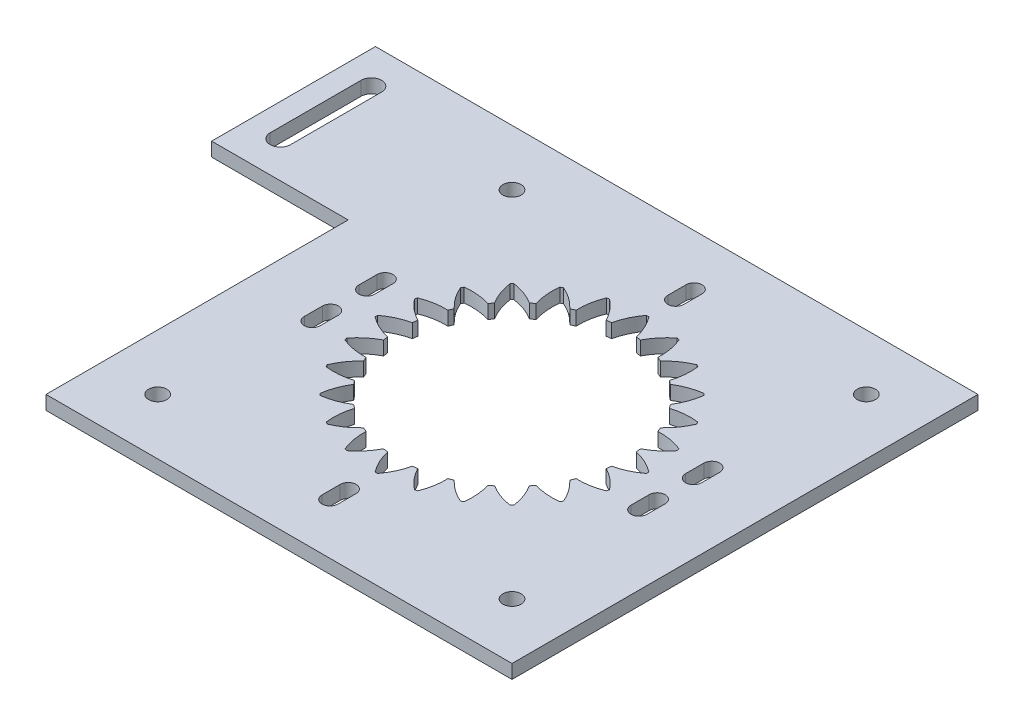
SolidWorks part; units mm, degrees
ref_plane "Front Plane" through (0, 0, 0) normal (0, 0, 1) x (1, 0, 0)
ref_plane "Top Plane" through (0, 0, 0) normal (0, 1, 0) x (1, 0, 0)
ref_plane "Right Plane" through (0, 0, 0) normal (1, 0, 0) x (0, 0, -1)
sketch "Sketch4" plane through (0, 0, 0) normal (0, 0, 1) x (1, 0, 0)
  line L0 (0, 0) -> (0, 40.0324) construction
sketch "Sketch1" plane through (0, 0, 0) normal (0, 1, 0) x (1, 0, 0)
  line L1 (-51.2, -51.2) -> (51.2, -51.2)
  line L2 (-51.2, -51.2) -> (-51.2, 15.2)
  line L3 (-51.2, 51.2) -> (51.2, 51.2)
  line L4 (51.2, -51.2) -> (51.2, 51.2)
  line L5 (-51.2, -51.2) -> (51.2, 51.2) construction
  line L6 (-51.2, 51.2) -> (51.2, -51.2) construction
  line L7 (-51.2, 51.2) -> (-81.2, 51.2)
  line L9 (-51.2, 15.2) -> (-81.2, 15.2)
  line L10 (-81.2, 51.2) -> (-81.2, 15.2)
  point P0 (0, 0)
  dimension "D1" = 102.4
  dimension "D2" = 102.4
  dimension "D3" = 30
  dimension "D4" = 36
extrude "Boss-Extrude1" add sketch "Sketch1" along normal blind 3.05
sketch "Sketch2" plane through (0, 3.05, 0) normal (0, 1, 0) x (1, 0, 0)
  arc B0 (7.4382, 28.8707) -> (3.7536, 24.4637) centre (15.7158, 18.2062) ccw
  arc B1 (7.9937, 28.7219) -> (7.4382, 28.8707) centre (0, 0) ccw
  arc B2 (8.9811, 23.063) -> (7.9937, 28.7219) centre (-4.5072, 23.6249) ccw
  arc B3 (9.9574, 22.6586) -> (8.9811, 23.063) centre (0, 0) ccw
  arc B4 (14.657, 25.9618) -> (9.9574, 22.6586) centre (19.8924, 13.5183) ccw
  arc B5 (15.1551, 25.6743) -> (14.657, 25.9618) centre (0, 0) ccw
  arc B6 (14.6443, 19.9527) -> (15.1551, 25.6743) centre (1.761, 23.9865) ccw
  arc B7 (15.4826, 19.3094) -> (14.6443, 19.9527) centre (0, 0) ccw
  arc B8 (20.877, 21.2837) -> (15.4826, 19.3094) centre (22.7134, 7.9092) ccw
  arc B9 (21.2837, 20.877) -> (20.877, 21.2837) centre (0, 0) ccw
  arc B10 (19.3094, 15.4826) -> (21.2837, 20.877) centre (7.9092, 22.7134) ccw
  arc B11 (19.9527, 14.6443) -> (19.3094, 15.4826) centre (0, 0) ccw
  arc B12 (25.6743, 15.1551) -> (19.9527, 14.6443) centre (23.9865, 1.761) ccw
  arc B13 (25.9618, 14.657) -> (25.6743, 15.1551) centre (0, 0) ccw
  arc B14 (22.6586, 9.9574) -> (25.9618, 14.657) centre (13.5183, 19.8924) ccw
  arc B15 (23.063, 8.9811) -> (22.6586, 9.9574) centre (0, 0) ccw
  arc B16 (28.7219, 7.9937) -> (23.063, 8.9811) centre (23.6249, -4.5072) ccw
  arc B17 (28.8707, 7.4382) -> (28.7219, 7.9937) centre (0, 0) ccw
  arc B18 (24.4637, 3.7536) -> (28.8707, 7.4382) centre (18.2062, 15.7158) ccw
  arc B19 (24.6016, 2.706) -> (24.4637, 3.7536) centre (0, 0) ccw
  arc B20 (29.8121, 0.2875) -> (24.6016, 2.706) centre (21.6534, -10.4682) ccw
  arc B21 (29.8121, -0.2875) -> (29.8121, 0.2875) centre (0, 0) ccw
  arc B22 (24.6016, -2.706) -> (29.8121, -0.2875) centre (21.6534, 10.4682) ccw
  arc B23 (24.4637, -3.7536) -> (24.6016, -2.706) centre (0, 0) ccw
  arc B24 (28.8707, -7.4382) -> (24.4637, -3.7536) centre (18.2062, -15.7158) ccw
  arc B25 (28.7219, -7.9937) -> (28.8707, -7.4382) centre (0, 0) ccw
  arc B26 (23.063, -8.9811) -> (28.7219, -7.9937) centre (23.6249, 4.5072) ccw
  arc B27 (22.6586, -9.9574) -> (23.063, -8.9811) centre (0, 0) ccw
  arc B28 (25.9618, -14.657) -> (22.6586, -9.9574) centre (13.5183, -19.8924) ccw
  arc B29 (25.6743, -15.1551) -> (25.9618, -14.657) centre (0, 0) ccw
  arc B30 (19.9527, -14.6443) -> (25.6743, -15.1551) centre (23.9865, -1.761) ccw
  arc B31 (19.3094, -15.4826) -> (19.9527, -14.6443) centre (0, 0) ccw
  arc B32 (21.2837, -20.877) -> (19.3094, -15.4826) centre (7.9092, -22.7134) ccw
  arc B33 (20.877, -21.2837) -> (21.2837, -20.877) centre (0, 0) ccw
  arc B34 (15.4826, -19.3094) -> (20.877, -21.2837) centre (22.7134, -7.9092) ccw
  arc B35 (14.6443, -19.9527) -> (15.4826, -19.3094) centre (0, 0) ccw
  arc B36 (15.1551, -25.6743) -> (14.6443, -19.9527) centre (1.761, -23.9865) ccw
  arc B37 (14.657, -25.9618) -> (15.1551, -25.6743) centre (0, 0) ccw
  arc B38 (9.9574, -22.6586) -> (14.657, -25.9618) centre (19.8924, -13.5183) ccw
  arc B39 (8.9811, -23.063) -> (9.9574, -22.6586) centre (0, 0) ccw
  arc B40 (7.9937, -28.7219) -> (8.9811, -23.063) centre (-4.5072, -23.6249) ccw
  arc B41 (7.4382, -28.8707) -> (7.9937, -28.7219) centre (0, 0) ccw
  arc B42 (3.7536, -24.4637) -> (7.4382, -28.8707) centre (15.7158, -18.2062) ccw
  arc B43 (2.706, -24.6016) -> (3.7536, -24.4637) centre (0, 0) ccw
  arc B44 (0.2875, -29.8121) -> (2.706, -24.6016) centre (-10.4682, -21.6534) ccw
  arc B45 (-0.2875, -29.8121) -> (0.2875, -29.8121) centre (0, 0) ccw
  arc B46 (-2.706, -24.6016) -> (-0.2875, -29.8121) centre (10.4682, -21.6534) ccw
  arc B47 (-3.7536, -24.4637) -> (-2.706, -24.6016) centre (0, 0) ccw
  arc B48 (-7.4382, -28.8707) -> (-3.7536, -24.4637) centre (-15.7158, -18.2062) ccw
  arc B49 (-7.9937, -28.7219) -> (-7.4382, -28.8707) centre (0, 0) ccw
  arc B50 (-8.9811, -23.063) -> (-7.9937, -28.7219) centre (4.5072, -23.6249) ccw
  arc B51 (-9.9574, -22.6586) -> (-8.9811, -23.063) centre (0, 0) ccw
  arc B52 (-14.657, -25.9618) -> (-9.9574, -22.6586) centre (-19.8924, -13.5183) ccw
  arc B53 (-15.1551, -25.6743) -> (-14.657, -25.9618) centre (0, 0) ccw
  arc B54 (-14.6443, -19.9527) -> (-15.1551, -25.6743) centre (-1.761, -23.9865) ccw
  arc B55 (-15.4826, -19.3094) -> (-14.6443, -19.9527) centre (0, 0) ccw
  arc B56 (-20.877, -21.2837) -> (-15.4826, -19.3094) centre (-22.7134, -7.9092) ccw
  arc B57 (-21.2837, -20.877) -> (-20.877, -21.2837) centre (0, 0) ccw
  arc B58 (-19.3094, -15.4826) -> (-21.2837, -20.877) centre (-7.9092, -22.7134) ccw
  arc B59 (-19.9527, -14.6443) -> (-19.3094, -15.4826) centre (0, 0) ccw
  arc B60 (-25.6743, -15.1551) -> (-19.9527, -14.6443) centre (-23.9865, -1.761) ccw
  arc B61 (-25.9618, -14.657) -> (-25.6743, -15.1551) centre (0, 0) ccw
  arc B62 (-22.6586, -9.9574) -> (-25.9618, -14.657) centre (-13.5183, -19.8924) ccw
  arc B63 (-23.063, -8.9811) -> (-22.6586, -9.9574) centre (0, 0) ccw
  arc B64 (-28.7219, -7.9937) -> (-23.063, -8.9811) centre (-23.6249, 4.5072) ccw
  arc B65 (-28.8707, -7.4382) -> (-28.7219, -7.9937) centre (0, 0) ccw
  arc B66 (-24.4637, -3.7536) -> (-28.8707, -7.4382) centre (-18.2062, -15.7158) ccw
  arc B67 (-24.6016, -2.706) -> (-24.4637, -3.7536) centre (0, 0) ccw
  arc B68 (-29.8121, -0.2875) -> (-24.6016, -2.706) centre (-21.6534, 10.4682) ccw
  arc B69 (-29.8121, 0.2875) -> (-29.8121, -0.2875) centre (0, 0) ccw
  arc B70 (-24.6016, 2.706) -> (-29.8121, 0.2875) centre (-21.6534, -10.4682) ccw
  arc B71 (-24.4637, 3.7536) -> (-24.6016, 2.706) centre (0, 0) ccw
  arc B72 (-28.8707, 7.4382) -> (-24.4637, 3.7536) centre (-18.2062, 15.7158) ccw
  arc B73 (-28.7219, 7.9937) -> (-28.8707, 7.4382) centre (0, 0) ccw
  arc B74 (-23.063, 8.9811) -> (-28.7219, 7.9937) centre (-23.6249, -4.5072) ccw
  arc B75 (-22.6586, 9.9574) -> (-23.063, 8.9811) centre (0, 0) ccw
  arc B76 (-25.9618, 14.657) -> (-22.6586, 9.9574) centre (-13.5183, 19.8924) ccw
  arc B77 (-25.6743, 15.1551) -> (-25.9618, 14.657) centre (0, 0) ccw
  arc B78 (-19.9527, 14.6443) -> (-25.6743, 15.1551) centre (-23.9865, 1.761) ccw
  arc B79 (-19.3094, 15.4826) -> (-19.9527, 14.6443) centre (0, 0) ccw
  arc B80 (-21.2837, 20.877) -> (-19.3094, 15.4826) centre (-7.9092, 22.7134) ccw
  arc B81 (-20.877, 21.2837) -> (-21.2837, 20.877) centre (0, 0) ccw
  arc B82 (-15.4826, 19.3094) -> (-20.877, 21.2837) centre (-22.7134, 7.9092) ccw
  arc B83 (-14.6443, 19.9527) -> (-15.4826, 19.3094) centre (0, 0) ccw
  arc B84 (-15.1551, 25.6743) -> (-14.6443, 19.9527) centre (-1.761, 23.9865) ccw
  arc B85 (-14.657, 25.9618) -> (-15.1551, 25.6743) centre (0, 0) ccw
  arc B86 (-9.9574, 22.6586) -> (-14.657, 25.9618) centre (-19.8924, 13.5183) ccw
  arc B87 (-8.9811, 23.063) -> (-9.9574, 22.6586) centre (0, 0) ccw
  arc B88 (-7.9937, 28.7219) -> (-8.9811, 23.063) centre (4.5072, 23.6249) ccw
  arc B89 (-7.4382, 28.8707) -> (-7.9937, 28.7219) centre (0, 0) ccw
  arc B90 (-3.7536, 24.4637) -> (-7.4382, 28.8707) centre (-15.7158, 18.2062) ccw
  arc B91 (-2.706, 24.6016) -> (-3.7536, 24.4637) centre (0, 0) ccw
  arc B92 (-0.2875, 29.8121) -> (-2.706, 24.6016) centre (10.4682, 21.6534) ccw
  arc B93 (0.2875, 29.8121) -> (-0.2875, 29.8121) centre (0, 0) ccw
  arc B94 (2.706, 24.6016) -> (0.2875, 29.8121) centre (-10.4682, 21.6534) ccw
  arc B95 (3.7536, 24.4637) -> (2.706, 24.6016) centre (0, 0) ccw
sketch_block_instance "Block1-1"
sketch_block "Block1"
extrude "Cut-Extrude1" cut sketch "Sketch2" against normal blind 10
sketch "Sketch3" plane through (0, 3.05, 0) normal (0, 1, 0) x (1, 0, 0)
  line L0 (51.2, -51.2) -> (51.2, 51.2) construction
  line L1 (51.2, 51.2) -> (-81.2, 51.2) construction
  circle A0 centre (38.93, 38.93) radius 2
  dimension "D3" = 4
  dimension "D1" = 12.27
  dimension "D2" = 12.27
extrude "Cut-Extrude2" cut sketch "Sketch3" against normal blind 10
pattern_circular "CirPattern1" count 4 over 360 about axis through (0, 0, 0) along (0, 1, 0) of "Cut-Extrude2"
sketch "Sketch7" plane through (0, 3.05, 0) normal (0, 1, 0) x (1, 0, 0)
  line L0 (-49.6947, 0) -> (47.5674, 0) construction
  line L1 (0, -37.2684) -> (0, -38.7316) construction
  line L2 (1.75, -37.2684) -> (1.75, -38.7316)
  line L3 (-1.75, -37.2684) -> (-1.75, -38.7316)
  line L4 (0, -40) -> (0, -36) construction
  line L5 (-1.75, -40) -> (-1.75, -36)
  line L6 (1.75, -40) -> (1.75, -36)
  arc A0 (1.75, -37.2684) -> (-1.75, -37.2684) centre (0, -37.2684) ccw
  arc A1 (-1.75, -38.7316) -> (1.75, -38.7316) centre (0, -38.7316) ccw
  arc A2 (-1.75, -40) -> (1.75, -40) centre (0, -40) ccw
  arc A3 (1.75, -36) -> (-1.75, -36) centre (0, -36) ccw
  point P5 (0, -38)
  point P12 (0, -38)
  dimension "D1" = 38
  dimension "D2" = 3.5
  dimension "D3" = 4
extrude "Cut-Extrude3" cut sketch "Sketch7" against normal up to surface (3.05 mm away) contours A3 L5 A2 L6 up to face at (38.93, 0, 36.93)
sketch "Sketch9" plane through (0, 3.05, 0) normal (0, 1, 0) x (1, 0, 0)
  line L0 (-54.2517, 0) -> (57.2543, 0) construction
  line L1 (35.9, -4) -> (35.9, -8) construction
  line L2 (37.65, -4) -> (37.65, -8)
  line L3 (34.15, -4) -> (34.15, -8)
  line L4 (51.2, -51.2) -> (51.2, 51.2) construction
  arc A0 (37.65, -4) -> (34.15, -4) centre (35.9, -4) ccw
  arc A1 (34.15, -8) -> (37.65, -8) centre (35.9, -8) ccw
  point P5 (35.9, -6)
  dimension "D3" = 15.3
  dimension "D1" = 3.5
  dimension "D2" = 4
  dimension "D4" = 6
extrude "Cut-Extrude4" cut sketch "Sketch9" against normal blind 10
mirror "Mirror1" about plane through (0, 0, 0) normal (1, 0, 0) of "Cut-Extrude4"
mirror "Mirror2" about plane through (0, 0, 0) normal (0, 0, 1) of "Cut-Extrude3", "Mirror1"
sketch "Sketch10" plane through (0, 3.05, 0) normal (0, 1, 0) x (1, 0, 0)
  line L0 (-74.11, 43.2) -> (-74.11, 23.2) construction
  line L1 (-71.86, 43.2) -> (-71.86, 23.2)
  line L2 (-76.36, 43.2) -> (-76.36, 23.2)
  line L3 (51.2, 51.2) -> (-81.2, 51.2) construction
  arc A0 (-71.86, 43.2) -> (-76.36, 43.2) centre (-74.11, 43.2) ccw
  arc A1 (-76.36, 23.2) -> (-71.86, 23.2) centre (-74.11, 23.2) ccw
  point P2 (-74.11, 33.2)
  dimension "D1" = 4.5
  dimension "D2" = 20
  dimension "D3" = 74.11
  dimension "D4" = 18
extrude "Cut-Extrude5" cut sketch "Sketch10" against normal blind 10
